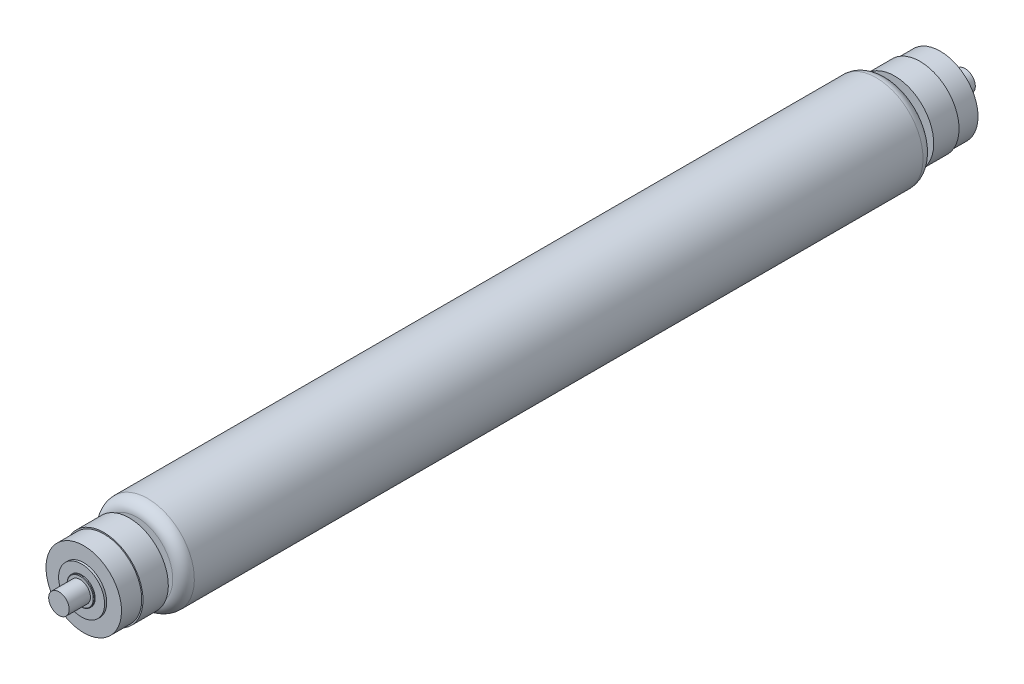
SolidWorks part; units mm, degrees
material "Nylon 6/10"
ref_plane "Front" through (0, 0, 0) normal (0, 0, 1) x (1, 0, 0)
ref_plane "Top" through (0, 0, 0) normal (0, 1, 0) x (1, 0, 0)
ref_plane "Right" through (0, 0, 0) normal (1, 0, 0) x (0, 0, -1)
sketch "Sketch3" plane through (0, 0, 0) normal (1, 0, 0) x (0, 0, -1)
  line L0 (-192.3288, -10.9855) -> (-20.8788, -10.9855)
  line L1 (-16.5608, -9.1821) -> (-10.6045, -9.1821)
  line L2 (-18.3388, -4.2073) -> (-18.3388, -8.4455)
  line L3 (-16.5608, -6.35) -> (-16.5608, -9.1821)
  line L4 (-18.3388, -9.5123) -> (-18.3388, -10.9855) construction
  line L5 (-106.6038, 0) -> (-106.6038, 4.5536) construction
  line L6 (-191.6938, -9.5123) -> (-191.6938, -10.9855) construction
  line L7 (-194.8688, -4.2073) -> (-196.6468, -6.35)
  line L8 (-21.5138, -9.5123) -> (-21.5138, -10.9855) construction
  line L9 (-5.842, -8.8847) -> (-10.6045, -8.8847)
  line L10 (-202.6031, -9.1821) -> (-202.6031, -8.8847)
  line L11 (-5.842, -8.8847) -> (-5.842, -5.4102)
  line L12 (-207.8736, -3.1927) -> (-208.0756, -3.1927)
  line L13 (-5.842, -5.4102) -> (-5.334, -5.4102)
  line L14 (-213.2076, -2.413) -> (-208.2038, -2.413)
  line L15 (-5.334, -5.4102) -> (-5.334, -3.1927)
  line L16 (-213.2076, -2.413) -> (-213.2076, 0)
  line L17 (-208.2038, -3.0645) -> (-208.2038, -2.413)
  line L18 (-208.2038, -3.0645) -> (-208.0756, -3.1927)
  line L19 (-5.0038, -3.0645) -> (-5.132, -3.1927)
  line L20 (-207.8736, -5.4102) -> (-207.8736, -3.1927)
  line L21 (-5.0038, -3.0645) -> (-5.0038, -2.413)
  line L22 (-207.3656, -5.4102) -> (-207.8736, -5.4102)
  line L23 (0, -2.413) -> (0, 0)
  line L24 (-207.3656, -8.8847) -> (-207.3656, -5.4102)
  line L25 (0, -2.413) -> (-5.0038, -2.413)
  line L26 (-207.3656, -8.8847) -> (-202.6031, -8.8847)
  line L27 (-5.334, -3.1927) -> (-5.132, -3.1927)
  line L28 (-10.6045, -9.1821) -> (-10.6045, -8.8847)
  line L29 (0, 0) -> (-33.2308, 0) construction
  line L30 (-196.6468, -6.35) -> (-196.6468, -9.1821)
  line L31 (-194.8688, -4.2073) -> (-194.8688, -8.4455)
  line L32 (-196.6468, -9.1821) -> (-202.6031, -9.1821)
  line L34 (-18.3388, -4.2073) -> (-16.5608, -6.35)
  line L35 (-213.2076, 0) -> (0, 0)
  line L37 (-208.2038, -119.75) -> (-208.2038, -101.6295) construction
  arc A0 (-18.3388, -8.4455) -> (-20.8788, -10.9855) centre (-20.8788, -8.4455) cw
  arc A1 (-194.8688, -8.4455) -> (-192.3288, -10.9855) centre (-192.3288, -8.4455) ccw
  dimension "D21" = 2.54
  dimension "D1" = 10.9855
  dimension "D3" = 16.5608
  dimension "D4" = 10.6045
  dimension "D5" = 5.842
  dimension "D6" = 5.334
  dimension "D7" = 5.0038
  dimension "D8" = 5.132
  dimension "D9" = 2.413
  dimension "D10" = 3.0645
  dimension "D11" = 3.1927
  dimension "D12" = 5.4102
  dimension "D13" = 8.8847
  dimension "D14" = 9.1821
  dimension "D15" = 6.35
  dimension "D16" = 5.0038
  dimension "D17" = 225
  dimension "D18" = 140.315
  dimension "D19" = 4.953
  dimension "D20" = 3.175
revolve "Revolve1" add sketch "Sketch3" angle 360 about L29
